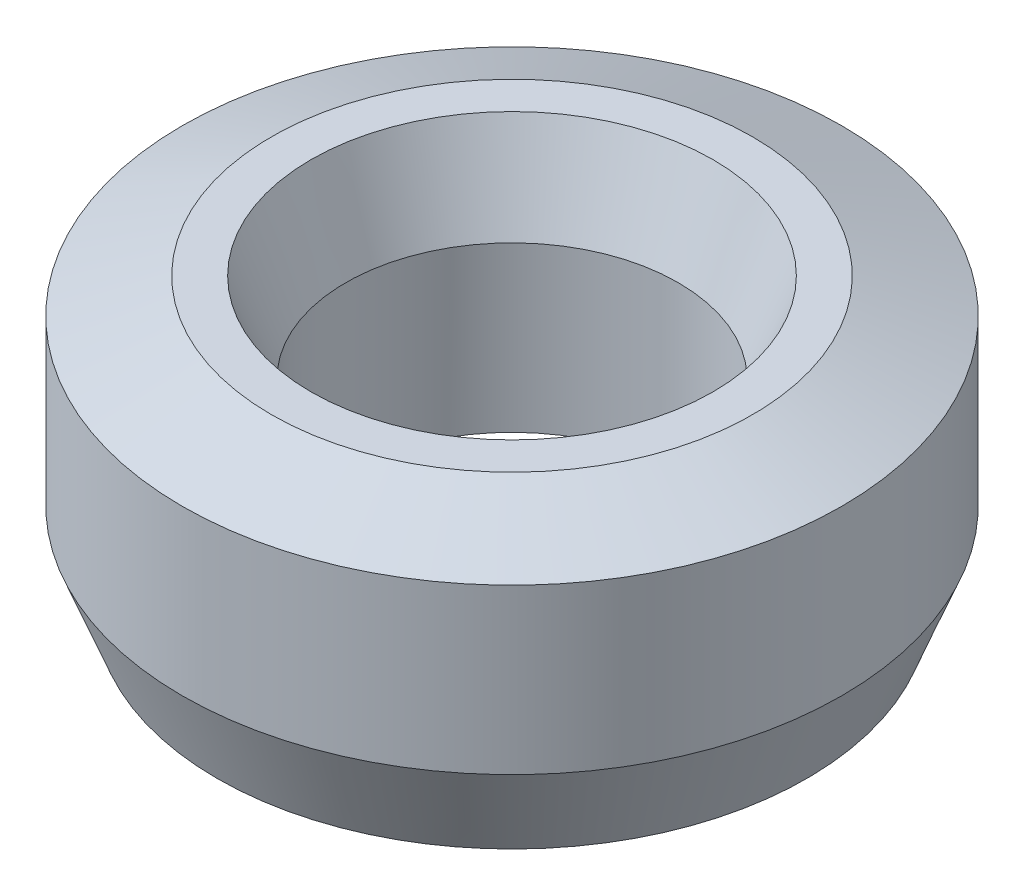
SolidWorks part; units mm, degrees
ref_plane "Front Plane" through (0, 0, 0) normal (0, 0, 1) x (1, 0, 0)
ref_plane "Top Plane" through (0, 0, 0) normal (0, 1, 0) x (1, 0, 0)
ref_plane "Right Plane" through (0, 0, 0) normal (1, 0, 0) x (0, 0, -1)
sketch "Sketch1" plane through (0, 0, 0) normal (0, 1, 0) x (1, 0, 0)
  circle A0 centre (0, 0) radius 35
  dimension "SLEEVE_OD" = 70
extrude "Boss-Extrude1" add sketch "Sketch1" along normal blind 30.5752
sketch "Sketch2" plane through (0, 0, 0) normal (0, 1, 0) x (1, 0, 0)
  circle A0 centre (0, 0) radius 17.6457
  dimension "BORE_D" = 35.2915
extrude "Cut-Extrude1" cut sketch "Sketch2" along normal through all
chamfer "Chamfer1" distance 3.7012 angle 68.622 4 edges at (0, 30.5752, 17.6457) (0, 0, 17.6457) (0, 0, 35) (0, 30.5752, 35) first distance on face at (0, 30.5752, 17.6457) first distance on face at (0, 0, 17.6457) first distance on face at (0, 30.5752, 35)
